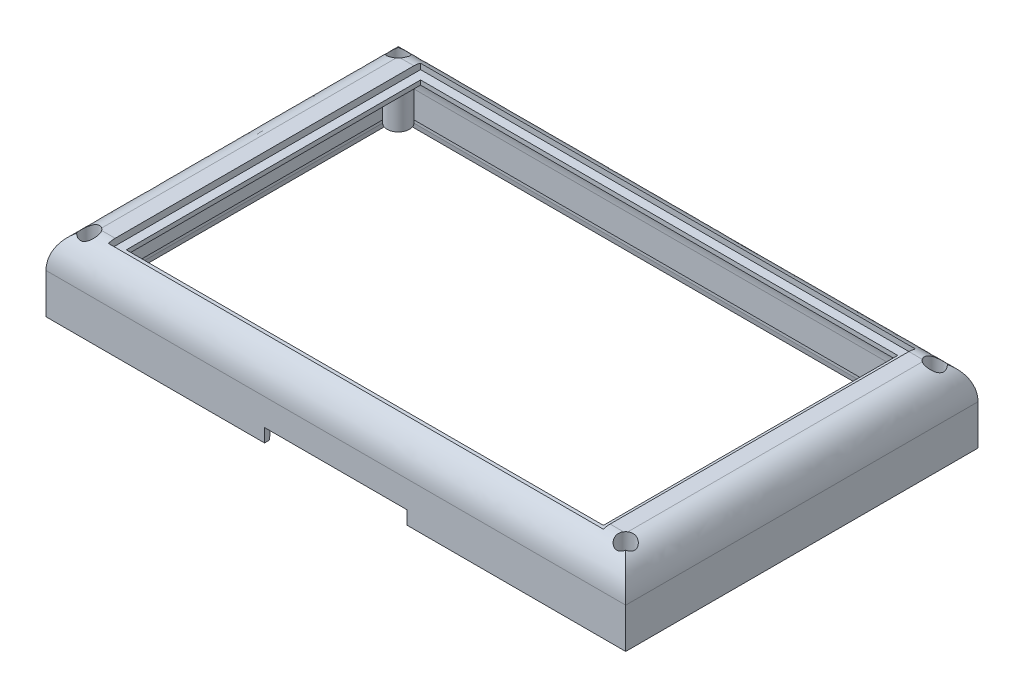
SolidWorks part; units mm, degrees
ref_plane "Front Plane" through (0, 0, 0) normal (0, 0, 1) x (1, 0, 0)
ref_plane "Top Plane" through (0, 0, 0) normal (0, 1, 0) x (1, 0, 0)
ref_plane "Right Plane" through (0, 0, 0) normal (1, 0, 0) x (0, 0, -1)
sketch "Sketch1" plane through (0, 0, 0) normal (0, 1, 0) x (1, 0, 0)
  line L1 (-65, 39.5) -> (65, 39.5)
  line L2 (-65, 39.5) -> (-65, -39.5)
  line L3 (-65, -39.5) -> (65, -39.5)
  line L4 (65, 39.5) -> (65, -39.5)
  line L5 (-65, 39.5) -> (65, -39.5) construction
  line L6 (-65, -39.5) -> (65, 39.5) construction
  point P0 (0, 0)
  dimension "D1" = 130
  dimension "D2" = 79
extrude "Boss-Extrude1" add sketch "Sketch1" along normal blind 17
fillet "Fillet1" radius 8 4 edges at (-65, 17, 0) (0, 17, 39.5) (0, 17, -39.5) (65, 17, 0)
shell "Shell5" thickness 2.5
sketch "Sketch2" plane through (0, 17, 0) normal (0, 1, 0) x (1, 0, 0)
  line L1 (-55.5, 35) -> (55.5, 35)
  line L2 (-55.5, 35) -> (-55.5, -35)
  line L3 (-55.5, -35) -> (55.5, -35)
  line L4 (55.5, 35) -> (55.5, -35)
  line L5 (-55.5, 35) -> (55.5, -35) construction
  line L6 (-55.5, -35) -> (55.5, 35) construction
  line L11 (-53.5, 33) -> (53.5, -33) construction
  line L12 (-53.5, -33) -> (53.5, 33) construction
  point P0 (0, 0)
  point P6 (0, 0)
  dimension "D1" = 111
  dimension "D2" = 70
  dimension "D3" = 107
  dimension "D4" = 66
extrude "Cut-Extrude1" cut sketch "Sketch2" against normal blind 1.5
sketch "Sketch3" plane through (0, 17, 0) normal (0, 1, 0) x (1, 0, 0)
  line L1 (-53.5, 33) -> (53.5, 33)
  line L2 (-53.5, 33) -> (-53.5, -33)
  line L3 (-53.5, -33) -> (53.5, -33)
  line L4 (53.5, 33) -> (53.5, -33)
  line L5 (-53.5, 33) -> (53.5, -33) construction
  line L6 (-53.5, -33) -> (53.5, 33) construction
  point P0 (0, 0)
  dimension "D1" = 107
  dimension "D2" = 66
extrude "Cut-Extrude3" cut sketch "Sketch3" against normal through all
sketch "Sketch11" plane through (0, 0, 0) normal (0, -1, 0) x (1, 0, 0)
  line L8 (63.75, -38.25) -> (63.75, 38.25)
  line L9 (63.75, 38.25) -> (-63.75, 38.25)
  line L10 (-63.75, 38.25) -> (-63.75, -38.25)
  line L11 (-63.75, -38.25) -> (63.75, -38.25)
  line L12 (63.75, -38.25) -> (63.75, 38.25)
  line L13 (63.75, 38.25) -> (-63.75, 38.25)
  line L14 (-63.75, 38.25) -> (-63.75, -38.25)
  line L15 (-63.75, -38.25) -> (63.75, -38.25)
  dimension "D1" = 1.25
extrude "Cut-Extrude4" cut sketch "Sketch11" against normal blind 3
chamfer "Chamfer1" distance 0.2 angle 80 4 edges at (0, 0, -38.25) (63.75, 0, 0) (0, 0, 38.25) (-63.75, 0, 0)
sketch "Sketch12" plane through (0, 3, 0) normal (0, -1, 0) x (1, 0, 0)
  line L0 (62.5, 37) -> (-62.5, 37) construction
  line L3 (-62.5, 37) -> (-62.5, -37) construction
  line L4 (-62.5, 35.5029) -> (-62.5, 37)
  line L5 (-62.5, 37) -> (-62.5, -37) construction
  line L6 (-62.5, 37) -> (-61.0029, 37)
  line L7 (62.5, 37) -> (-62.5, 37) construction
  line L8 (-65, 0) -> (65, 0) construction
  line L9 (-65, -39.5) -> (-65, 39.5) construction
  line L10 (65, 39.5) -> (65, -39.5) construction
  line L11 (0, -39.5) -> (0, 39.5) construction
  line L12 (-65, 39.5) -> (65, 39.5) construction
  line L13 (65, -39.5) -> (-65, -39.5) construction
  line L14 (62.5, 35.5029) -> (62.5, 37)
  line L15 (62.5, 37) -> (61.0029, 37)
  line L16 (62.5, -37) -> (61.0029, -37)
  line L17 (62.5, -35.5029) -> (62.5, -37)
  line L18 (-62.5, -35.5029) -> (-62.5, -37)
  line L19 (-62.5, -37) -> (-61.0029, -37)
  arc A0 (-62.5, 35.5029) -> (-61.0029, 37) centre (-60.15, 34.65) ccw
  arc A1 (62.5, 35.5029) -> (61.0029, 37) centre (60.15, 34.65) cw
  arc A2 (62.5, -35.5029) -> (61.0029, -37) centre (60.15, -34.65) ccw
  arc A3 (-62.5, -35.5029) -> (-61.0029, -37) centre (-60.15, -34.65) cw
  dimension "D1" = 5
  dimension "D2" = 2.35
  dimension "D3" = 2.35
extrude "Boss-Extrude2" add sketch "Sketch12" against normal up to body separate body
sketch "Sketch13" plane through (0, 17, 0) normal (0, 1, 0) x (1, 0, 0)
  line L0 (-65, 0) -> (65, 0) construction
  line L1 (-65, 39.5) -> (-65, -39.5) construction
  line L2 (65, -39.5) -> (65, 39.5) construction
  line L3 (0, -39.5) -> (0, 39.5) construction
  line L4 (-65, -39.5) -> (65, -39.5) construction
  line L5 (65, 39.5) -> (-65, 39.5) construction
  circle A0 centre (-60.15, -34.65) radius 2
  circle A1 centre (60.15, -34.65) radius 2
  circle A2 centre (60.15, 34.65) radius 2
  circle A3 centre (-60.15, 34.65) radius 2
  dimension "D1" = 4
extrude "Cut-Extrude5" cut sketch "Sketch13" against normal blind 10
sketch "Sketch15" plane through (0, 0, 39.5) normal (0, 0, 1) x (1, 0, 0)
  line L0 (63.75, 3) -> (-63.75, 3) construction
  line L1 (-15.99, 3) -> (15.99, 3)
  line L2 (-15.99, 3) -> (-15.99, -4.98)
  line L3 (-15.99, -4.98) -> (15.99, -4.98)
  line L4 (15.99, 3) -> (15.99, -4.98)
  line L5 (-15.99, 3) -> (15.99, -4.98) construction
  line L6 (-15.99, -4.98) -> (15.99, 3) construction
  point P0 (0, -0.99)
  point P5 (0, 0)
  dimension "D1" = 31.98
  dimension "D2" = 7.98
extrude "Cut-Extrude6" cut sketch "Sketch15" against normal up to surface (2.5 mm away) up to face at (14.8243, 6, 37)
sketch "Sketch14" plane through (0, 0, 37) normal (0, 0, -1) x (-1, 0, 0)
  line L0 (15.99, -4.98) -> (-15.99, -4.98) construction
  line L1 (20.7, 7.81) -> (-20.7, 7.81)
  line L2 (20.7, 7.81) -> (20.7, -16.49)
  line L3 (20.7, -16.49) -> (-20.7, -16.49)
  line L4 (-20.7, 7.81) -> (-20.7, -16.49)
  line L5 (20.7, 7.81) -> (-20.7, -16.49) construction
  line L6 (20.7, -16.49) -> (-20.7, 7.81) construction
  point P0 (0, -4.34)
  point P5 (0, 0)
  point P6 (0, 0)
  dimension "D1" = 41.4
  dimension "D2" = 24.3
  dimension "D3" = 11.51
extrude "Cut-Extrude7" cut sketch "Sketch14" against normal blind 1.25
